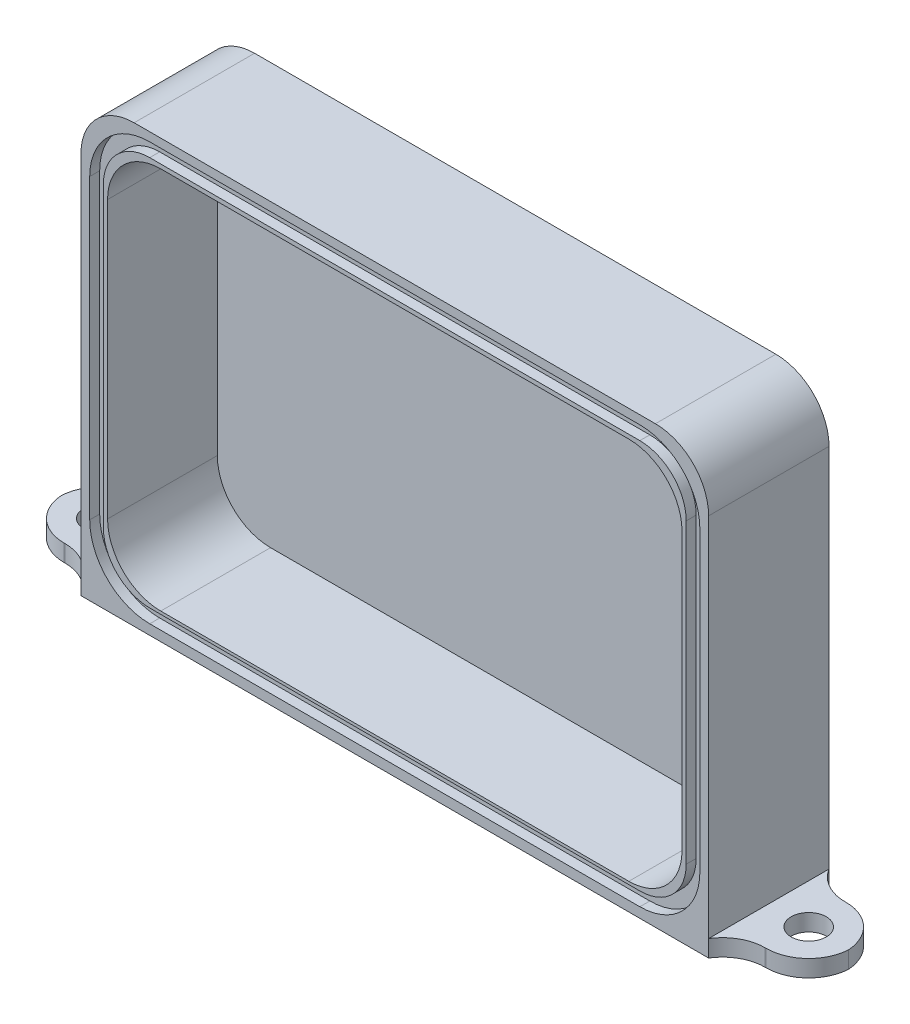
SolidWorks part; units mm, degrees
material "Custom Plastic"
ref_plane "X-Y Datum" through (0, 0, 0) normal (0, 0, 1) x (1, 0, 0)
ref_plane "X-Z Datum" through (0, 0, 0) normal (0, 1, 0) x (1, 0, 0)
ref_plane "Y-Z Datum" through (0, 0, 0) normal (1, 0, 0) x (0, 0, -1)
sketch "Sketch2" plane through (0, 0, 0) normal (0, 0, 1) x (1, 0, 0)
  line L1 (-54, 36) -> (54, 36)
  line L2 (-54, 36) -> (-54, -36)
  line L3 (-54, -36) -> (54, -36)
  line L4 (54, 36) -> (54, -36)
  line L5 (-54, 36) -> (54, -36) construction
  line L6 (-54, -36) -> (54, 36) construction
  point P0 (0, 0)
  dimension "D1" = 72
  dimension "D2" = 108
extrude "Boss-Extrude1" add sketch "Sketch2" along normal blind 20.64
shell "Shell1" thickness 5 removed face at (0, 0, 20.64) outward yes
sketch "Sketch3" plane through (0, 0, -5) normal (0, 0, -1) x (-1, 0, 0)
  line L4 (59, 41) -> (-59, 41)
  line L5 (-59, 41) -> (-59, -41)
  line L6 (-59, -41) -> (59, -41)
  line L7 (59, -41) -> (59, 41)
  line L8 (59, 41) -> (-59, 41)
  line L9 (-59, 41) -> (-59, -41)
  line L10 (-59, -41) -> (59, -41)
  line L11 (59, -41) -> (59, 41)
  dimension "D1" = 0
extrude "Cut-Extrude1" cut sketch "Sketch3" against normal blind 3
sketch "Sketch4" plane through (0, -41, 0) normal (0, -1, 0) x (1, 0, 0)
  line L0 (-59, 16.82) -> (-59, 1.82)
  line L1 (-59, 1.82) -> (-74, 1.82)
  line L2 (-74, 1.82) -> (-74, 16.82)
  line L3 (-74, 16.82) -> (-59, 16.82)
  line L4 (59, 16.82) -> (74, 16.82)
  line L5 (74, 16.82) -> (74, 1.82)
  line L6 (74, 1.82) -> (59, 1.82)
  line L7 (59, 1.82) -> (59, 16.82)
  line L8 (-66.5, 16.82) -> (-66.5, 1.82) construction
  line L9 (-74, 9.32) -> (-59, 9.32) construction
  line L10 (66.5, 16.82) -> (66.5, 1.82) construction
  line L11 (59, 9.32) -> (74, 9.32) construction
  line L12 (-59, 9.32) -> (59, 9.32) construction
  line L13 (-59, 20.64) -> (-59, -2) construction
  line L14 (59, -2) -> (-59, -2) construction
  line L15 (59, 20.64) -> (59, -2) construction
  circle A1 centre (-66.5, 9.32) radius 3.3
  circle A2 centre (66.5, 9.32) radius 3.3
  dimension "D2" = 6.6
  dimension "D3" = 15
  dimension "D1" = 15
  dimension "D4" = 3.82
extrude "Boss-Extrude2" add sketch "Sketch4" against normal blind 3.175
fillet "Fillet1" radius 10 6 edges at (59, 41, 9.32) (-59, 41, 9.32) (54, -36, 10.32) (-54, -36, 10.32) (54, 36, 10.32) (-54, 36, 10.32)
sketch "Sketch5" plane through (0, 0, 20.64) normal (0, 0, 1) x (1, 0, 0)
  line L0 (-46.0711, 38.0711) -> (46.0711, 38.0711) construction
  line L5 (56.0711, 28.0711) -> (56.0711, -27.825) construction
  line L6 (46.0711, -37.825) -> (-46.0711, -37.825) construction
  line L7 (-56.0711, -27.825) -> (-56.0711, 28.0711) construction
  line L8 (46.0711, -39.11) -> (-46.0711, -39.11)
  line L9 (-57.3561, -27.825) -> (-57.3561, 28.0711)
  line L10 (-46.0711, 39.3561) -> (46.0711, 39.3561)
  line L11 (57.3561, 28.0711) -> (57.3561, -27.825)
  line L12 (46.0711, -36.54) -> (-46.0711, -36.54)
  line L13 (-54.7861, -27.825) -> (-54.7861, 28.0711)
  line L14 (-46.0711, 36.7861) -> (46.0711, 36.7861)
  line L15 (54.7861, 28.0711) -> (54.7861, -27.825)
  line L16 (-44, -36) -> (44, -36) construction
  arc A0 (-49, 41) -> (-59, 31) centre (-49, 31) ccw construction
  arc A1 (59, 31) -> (49, 41) centre (49, 31) ccw construction
  arc A2 (56.0711, -27.825) -> (46.0711, -37.825) centre (46.0711, -27.825) cw construction
  arc A3 (46.0711, 38.0711) -> (56.0711, 28.0711) centre (46.0711, 28.0711) cw construction
  arc A4 (-46.0711, 38.0711) -> (-56.0711, 28.0711) centre (-46.0711, 28.0711) ccw construction
  arc A5 (-46.0711, -37.825) -> (-56.0711, -27.825) centre (-46.0711, -27.825) cw construction
  arc A6 (-46.0711, -39.11) -> (-57.3561, -27.825) centre (-46.0711, -27.825) cw
  arc A7 (-46.0711, 39.3561) -> (-57.3561, 28.0711) centre (-46.0711, 28.0711) ccw
  arc A8 (46.0711, 39.3561) -> (57.3561, 28.0711) centre (46.0711, 28.0711) cw
  arc A9 (57.3561, -27.825) -> (46.0711, -39.11) centre (46.0711, -27.825) cw
  arc A10 (-46.0711, -36.54) -> (-54.7861, -27.825) centre (-46.0711, -27.825) cw
  arc A11 (-46.0711, 36.7861) -> (-54.7861, 28.0711) centre (-46.0711, 28.0711) ccw
  arc A12 (46.0711, 36.7861) -> (54.7861, 28.0711) centre (46.0711, 28.0711) cw
  arc A13 (54.7861, -27.825) -> (46.0711, -36.54) centre (46.0711, -27.825) cw
  point P18 (56.0711, 38.0711)
  point P21 (-56.0711, 38.0711)
  dimension "D1" = 10
  dimension "D4" = 1.825
  dimension "D2" = 1.285
  dimension "D3" = 1.285
fillet "Fillet2" radius 8 8 edges at (74, -39.4125, 16.82) (59, -39.4125, 16.82) (74, -39.4125, 1.82) (59, -39.4125, 1.82) (-59, -39.4125, 1.82) (-74, -39.4125, 1.82) (-74, -39.4125, 16.82) (-59, -39.4125, 16.82)
extrude "Cut-Extrude2" cut sketch "Sketch5" against normal blind 1.875
